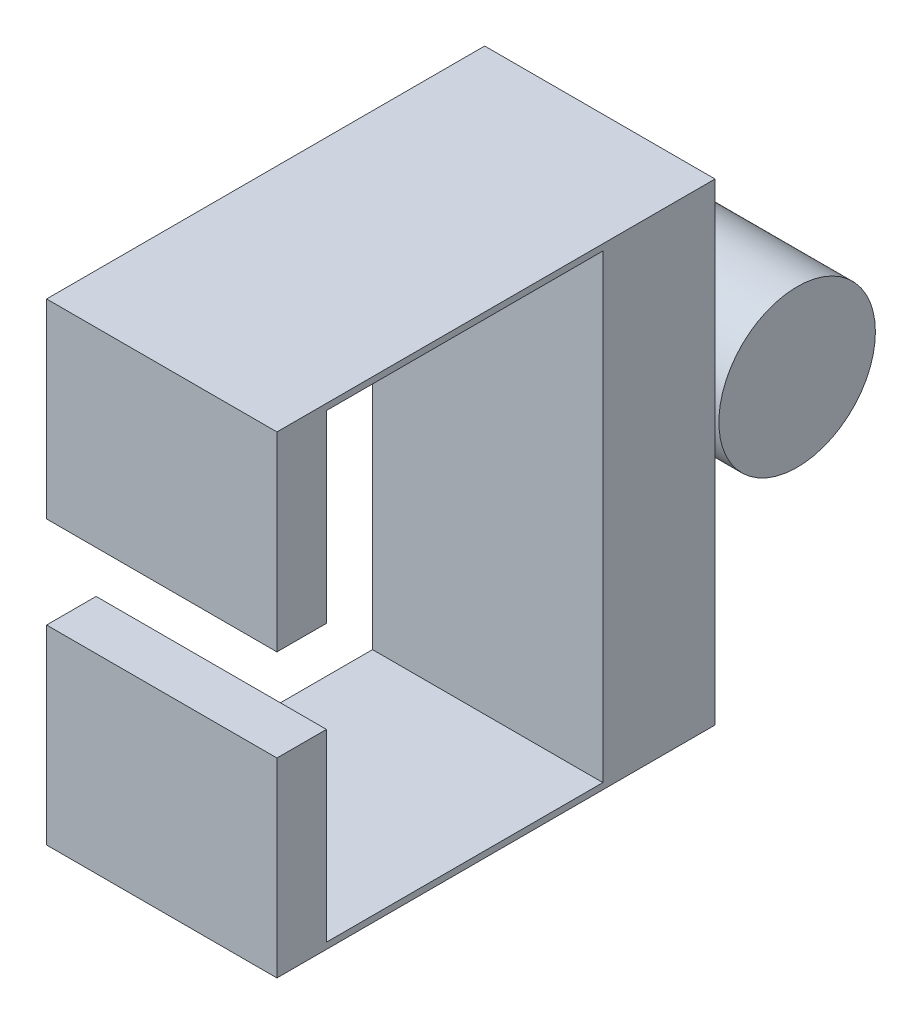
SolidWorks part; units mm, degrees
ref_plane "Front Plane" through (0, 0, 0) normal (1, 0, 0) x (0, 1, 0)
ref_plane "Top Plane" through (0, 0, 0) normal (0, 0, 1) x (0, 1, 0)
ref_plane "Right Plane" through (0, 0, 0) normal (0, 1, 0) x (-1, 0, 0)
sketch "Sketch1" plane through (0, 0, 0) normal (1, 0, 0) x (0, 1, 0)
  circle A0 centre (0, 0) radius 10.7897
  dimension "D1" = 21.5794
extrude "Boss-Extrude1" add sketch "Sketch1" along normal blind 25.4
sketch "Sketch2" plane through (0, 0, 0) normal (-1, 0, 0) x (0, -1, 0)
  line L0 (0, -10.7897) -> (12.7, -10.7897) construction
  line L1 (2.54, -10.7897) -> (-2.54, -10.7897)
  line L2 (12.7, -0.6297) -> (12.7, 14.6103)
  line L3 (-12.7, -0.6297) -> (-12.7, 14.6103)
  line L4 (12.7, 14.6103) -> (-12.7, 14.6103)
  circle A0 centre (0, 0) radius 10.7897 construction
  arc A1 (12.7, -0.6297) -> (2.54, -10.7897) centre (2.54, -0.6297) cw
  arc A2 (-2.54, -10.7897) -> (-12.7, -0.6297) centre (-2.54, -0.6297) cw
  point P12 (-12.7, -10.7897)
  dimension "D4" = 10.16
  dimension "D1" = 12.7
extrude "Boss-Extrude2" add sketch "Sketch2" along normal blind 3.0568
sketch "Sketch3" plane through (0, 0, 14.6103) normal (0, 0, 1) x (1, 0, 0)
  line L0 (-3.0568, 0) -> (-3.0568, 32.5938) construction
  line L1 (-3.0568, -12.7) -> (-3.0568, 12.7) construction
  line L2 (-3.0568, 32.5938) -> (-3.0568, -32.5938)
  line L3 (-3.0568, 32.5938) -> (28.6932, 32.5938)
  line L4 (-3.0568, -32.5938) -> (28.6932, -32.5938)
  line L5 (28.6932, 32.5938) -> (28.6932, -32.5938)
  dimension "D1" = 32.5938
  dimension "D2" = 65.1876
  dimension "D3" = 31.75
extrude "Boss-Extrude3" add sketch "Sketch3" along normal blind 15.4634
sketch "Sketch4" plane through (0, 0, 30.0736) normal (0, 0, 1) x (1, 0, 0)
  line L0 (-3.0568, 32.5938) -> (28.6932, 32.5938)
  line L1 (-3.0568, 32.5938) -> (-3.0568, 31.7297)
  line L2 (28.6932, 32.5938) -> (28.6932, 31.7297)
  line L3 (-3.0568, 31.7297) -> (28.6932, 31.7297)
  line L4 (28.6932, 32.5938) -> (-3.0568, 32.5938) construction
  dimension "D1" = 31.75
extrude "Boss-Extrude4" add sketch "Sketch4" along normal blind 44.9253 separate body
sketch "Sketch5" plane through (0, 31.7297, 0) normal (0, -1, 0) x (1, 0, 0)
  line L0 (-3.0568, 74.999) -> (28.6932, 74.999)
  line L1 (-3.0568, 74.999) -> (-3.0568, 68.1736)
  line L2 (28.6932, 74.999) -> (28.6932, 68.1736)
  line L3 (-3.0568, 68.1736) -> (28.6932, 68.1736)
  line L4 (-3.0568, 74.999) -> (28.6932, 74.999) construction
  dimension "D1" = 31.75
  dimension "D2" = 6.8253
extrude "Boss-Extrude5" add sketch "Sketch5" along normal blind 25.4
mirror "Mirror1" about plane through (0, 0, 0) normal (0, 1, 0) of bodies 105
combine bodies "Combine1" operation type add bodies to combine 105 103 106
equation "\"F\"= 600'Force"
equation "\"w\"= 2 * ( \"F\" )'Total Force"
equation "\"SF\"= 4'Safety Factor"
equation "\"Sy\"= 39885.37799'Yield Strength"
equation "\"E\"= 10007604'Elastic Modulus"
equation "\"a\"= 0.499in'Width of T Mount Arm"
equation "\"b\"= 0.9997in'Width of T Mount flat part"
equation "\"c\"= 1.5in'Height of T Mount flat part"
equation "\"TW\"= \"a\" + 2 * ( \"b\" )'Total width of T mount flat part"
equation "\"SA\"= \"Sy\" / \"SF\"'Allowed Stress"
equation "\"La\"= 1in'Length Part A"
equation "\"Za\"= ( \"SF\" * \"w\" * \"La\" ) / ( 2 * ( \"Sy\" ) )'Section Modulus Part A"
equation "\"ra\"= ( 4 * ( \"Za\" / 3.14 ) ) ^ ( 1 / 3 )'Radius Part A"
equation "\"da\"= 2 * ( \"ra\" )'Diameter Part A"
equation "\"wb\"= 1in'Width Part B"
equation "\"Lb\"= 1in'Length Part B"
equation "\"CSAb\"= \"w\" / \"SA\"'Cross Sectional Area Part B"
equation "\"tb\"= \"CSAb\" / \"wb\"'Thickness Part B"
equation "\"Lc\"= \"TW\" + 2 * ( \"Ld\" )'Length Part C"
equation "\"wc\"= 1.25in'Width Part C"
equation "\"Mc\"= ( \"w\" * \"Lc\" ) / 4'Bending Moment Part C"
equation "\"Zc\"= \"Mc\" / \"SA\"'Section Modulus Part C"
equation "\"hc\"= ( ( 6 * ( \"Zc\" ) ) / ( \"wc\" ) ) ^ ( 1 / 2 )'Height Part C"
equation "\"hd\"= \"c\" + \"he\"'Height Part D"
equation "\"wd\"= 1.25in'Width Part D"
equation "\"CSAd\"= \"F\" / \"SA\"'Cross Sectional Area Part D"
equation "\"Ld\" = \"CSAd\" / \"hd\"'Length Part D"
equation "\"Le\"= 1in'Length Part E"
equation "\"we\"= 1.25in'Width Part E"
equation "\"Me\"= ( \"F\" * \"Le\" ) / ( 4 )'Bending Moment Part E"
equation "\"Ze\"= \"Me\" / \"SA\"'Sectional Modulus Part E"
equation "\"he\"= ( ( 6 * ( \"Ze\" ) ) / ( \"we\" ) ) ^ ( 1 / 2 )'Height Part E"
equation "\"D1@Sketch1\"=\"da\""
equation "\"D1@Boss-Extrude1\"=\"La\""
equation "\"D1@Sketch2\"=\"wb\"/2"
equation "\"D2@Sketch2\"=\"wb\""
equation "\"D3@Sketch2\"=\"Lb\""
equation "\"D1@Boss-Extrude2\"=\"tb\""
equation "\"D1@Sketch3\"=\"Lc\"/2"
equation "\"D2@Sketch3\"=\"Lc\""
equation "\"D3@Sketch3\"=\"wc\""
equation "\"D1@Boss-Extrude3\"=\"hc\""
equation "\"D1@Sketch4\"=\"we\""
equation "\"D2@Sketch4\"=\"Ld\""
equation "\"D1@Boss-Extrude4\"=\"hd\""
equation "\"D1@Sketch5\"=\"we\""
equation "\"D2@Sketch5\"=\"he\""
equation "\"D1@Boss-Extrude5\"=\"Le\""
